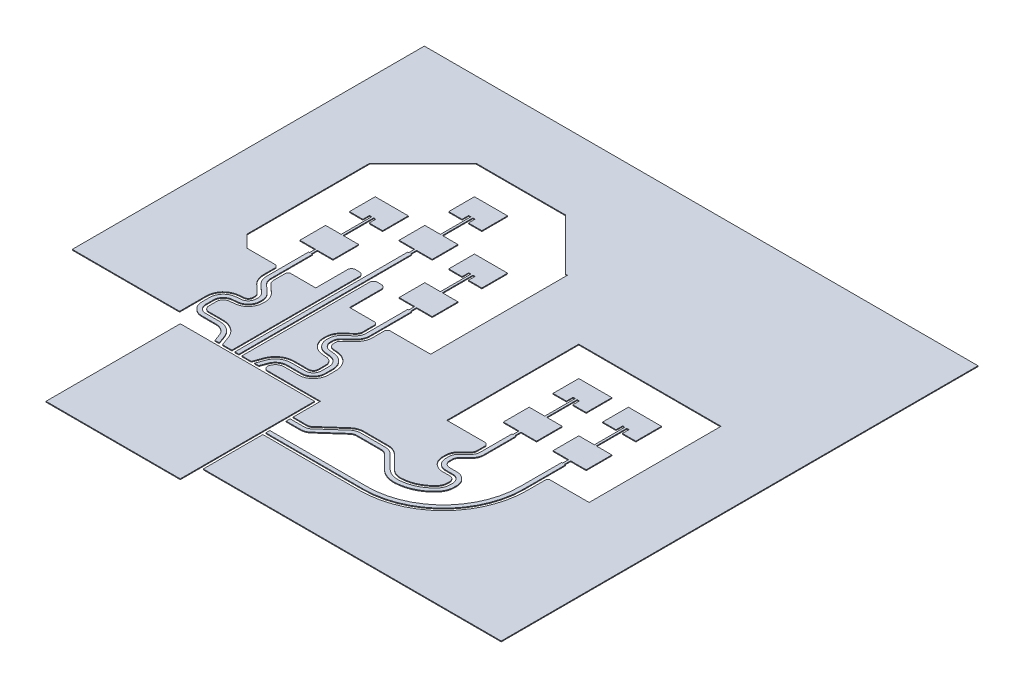
SolidWorks part; units mm, degrees
ref_plane "Front Plane" through (0, 0, 0) normal (0, 0, 1) x (1, 0, 0)
ref_plane "Top Plane" through (0, 0, 0) normal (0, 1, 0) x (1, 0, 0)
ref_plane "Right Plane" through (0, 0, 0) normal (1, 0, 0) x (0, 0, -1)
sketch "Sketch2" plane through (0, 0, 0) normal (0, 1, 0) x (1, 0, 0)
  line L1 (0, 0) -> (0.783, 0)
  line L2 (0, 0) -> (0, 1.294)
  line L3 (0, 1.294) -> (0.783, 1.294)
  line L4 (1.666, 0) -> (1.666, 1.294)
  line L6 (0.783, 1.294) -> (0.783, 2.8313)
  line L8 (0.883, 1.294) -> (0.883, 2.8313)
  line L9 (0.672, 2.8313) -> (0.783, 2.8313)
  line L11 (0, 3.792) -> (1.666, 3.792)
  line L13 (0, 2.498) -> (0.672, 2.498)
  line L14 (0.672, 2.498) -> (0.672, 2.8313)
  line L15 (0.883, 1.294) -> (1.666, 1.294)
  line L16 (0.883, 2.8313) -> (0.994, 2.8313)
  line L17 (0, 1.294) -> (1.666, 0) construction
  line L18 (0, 0) -> (1.666, 1.294) construction
  line L19 (0.833, -1.1816) -> (0.833, 2.0481) construction
  line L20 (0.994, 2.498) -> (0.994, 2.8313)
  line L21 (1.666, 2.498) -> (0.994, 2.498)
  line L23 (0, 3.792) -> (0, 2.498)
  line L24 (0.783, 1.294) -> (0.833, 1.294) construction
  line L25 (0.833, 1.294) -> (0.883, 1.294) construction
  line L26 (1.666, 3.792) -> (1.666, 2.498)
  line L27 (0, 3.792) -> (1.666, 2.498) construction
  line L28 (2.498, 6.29) -> (2.498, 4.996)
  line L29 (4.164, 4.996) -> (3.492, 4.996)
  line L30 (4.164, 2.498) -> (4.164, 3.792)
  line L31 (3.381, 5.3293) -> (3.492, 5.3293)
  line L32 (2.498, 2.498) -> (2.498, 3.792)
  line L33 (3.281, 3.792) -> (3.281, 5.3293)
  line L34 (2.498, 6.29) -> (4.164, 6.29)
  line L35 (2.498, 2.498) -> (4.164, 3.792) construction
  line L36 (3.17, 4.996) -> (3.17, 5.3293)
  line L37 (2.498, 4.996) -> (3.17, 4.996)
  line L38 (3.381, 3.792) -> (3.381, 5.3293)
  line L39 (3.381, 3.792) -> (4.164, 3.792)
  line L40 (2.498, 2.498) -> (3.281, 2.498)
  line L41 (2.498, 3.792) -> (3.281, 3.792)
  line L42 (4.164, 6.29) -> (4.164, 4.996)
  line L43 (3.17, 5.3293) -> (3.281, 5.3293)
  line L44 (3.492, 4.996) -> (3.492, 5.3293)
  line L45 (3.331, 6.29) -> (3.331, 2.498) construction
  line L46 (5.668, 2.8313) -> (5.779, 2.8313)
  line L47 (4.996, 0) -> (4.996, 1.294)
  line L48 (5.99, 2.498) -> (5.99, 2.8313)
  line L49 (5.668, 2.498) -> (5.668, 2.8313)
  line L50 (5.879, 1.294) -> (5.879, 2.8313)
  line L51 (4.996, 1.294) -> (5.779, 1.294)
  line L52 (5.879, 2.8313) -> (5.99, 2.8313)
  line L53 (6.662, 0) -> (6.662, 1.294)
  line L54 (6.662, 3.792) -> (6.662, 2.498)
  line L55 (5.879, 1.294) -> (6.662, 1.294)
  line L56 (4.996, 3.792) -> (4.996, 2.498)
  line L57 (6.662, 2.498) -> (5.99, 2.498)
  line L58 (4.996, 0) -> (5.779, 0)
  line L59 (5.779, 1.294) -> (5.779, 2.8313)
  line L60 (4.996, 2.498) -> (5.668, 2.498)
  line L61 (4.996, 3.792) -> (6.662, 3.792)
  line L62 (5.829, 3.792) -> (5.829, 0) construction
  line L63 (1.666, 2.498) -> (2.498, 2.498) construction
  line L64 (4.164, 2.498) -> (4.996, 2.498) construction
  line L65 (13.721, 0.0293) -> (13.832, 0.0293)
  line L66 (13.721, -0.304) -> (13.721, 0.0293)
  line L67 (13.832, -1.508) -> (13.832, 0.0293)
  line L68 (13.049, -1.508) -> (13.832, -1.508)
  line L69 (14.715, -2.802) -> (14.715, -1.508)
  line L70 (13.932, -1.508) -> (14.715, -1.508)
  line L71 (13.049, -0.304) -> (13.721, -0.304)
  line L72 (13.049, -2.802) -> (13.832, -2.802)
  line L73 (13.049, -2.802) -> (13.049, -1.508)
  line L74 (13.049, 0.99) -> (14.715, 0.99)
  line L75 (14.043, -0.304) -> (14.043, 0.0293)
  line L76 (14.715, -0.304) -> (14.043, -0.304)
  line L77 (13.932, -1.508) -> (13.932, 0.0293)
  line L78 (14.715, 0.99) -> (14.715, -0.304)
  line L79 (13.932, 0.0293) -> (14.043, 0.0293)
  line L80 (13.049, 0.99) -> (13.049, -0.304)
  line L81 (13.882, 0.99) -> (13.882, -2.802) construction
  line L82 (16.33, -1.508) -> (16.33, 0.0293)
  line L83 (15.547, -2.802) -> (15.547, -1.508)
  line L84 (15.547, -1.508) -> (16.33, -1.508)
  line L85 (15.547, -2.802) -> (16.33, -2.802)
  line L86 (16.541, -0.304) -> (16.541, 0.0293)
  line L87 (17.213, 0.99) -> (17.213, -0.304)
  line L88 (15.547, 0.99) -> (17.213, 0.99)
  line L89 (16.38, 0.99) -> (16.38, -2.802) construction
  line L90 (17.213, -2.802) -> (17.213, -1.508)
  line L91 (15.547, 0.99) -> (15.547, -0.304)
  line L92 (17.213, -0.304) -> (16.541, -0.304)
  line L93 (16.219, -0.304) -> (16.219, 0.0293)
  line L94 (15.547, -0.304) -> (16.219, -0.304)
  line L95 (16.43, -1.508) -> (17.213, -1.508)
  line L96 (16.43, -1.508) -> (16.43, 0.0293)
  line L97 (16.43, 0.0293) -> (16.541, 0.0293)
  line L98 (16.219, 0.0293) -> (16.33, 0.0293)
  line L99 (14.715, -0.304) -> (15.547, -0.304) construction
  line L100 (13.049, 0.99) -> (17.213, -2.802) construction
  line L101 (13.049, -2.802) -> (17.213, 0.99) construction
  line L102 (14.715, -2.802) -> (15.547, -2.802) construction
  line L103 (15.131, -2.802) -> (15.131, -0.906) construction
  line L104 (0.783, 0) -> (0.783, -0.3)
  line L105 (0.783, -0.3) -> (0.733, -0.3)
  line L106 (0.733, -0.3) -> (0.733, -1.681)
  line L107 (1.3338, -3.2667) -> (1.402, -3.1936) construction
  line L108 (0.933, -1.1816) -> (0.933, -0.3)
  line L109 (0.933, -0.3) -> (0.883, -0.3)
  line L110 (0.883, -0.3) -> (0.883, 0)
  line L111 (3.281, 2.498) -> (3.281, 2.198)
  line L112 (3.281, 2.198) -> (3.231, 2.198)
  line L113 (3.231, 2.198) -> (3.231, -6.502)
  line L114 (3.231, -6.502) -> (3.431, -6.502)
  line L115 (3.431, -6.502) -> (3.431, 2.198)
  line L116 (3.431, 2.198) -> (3.381, 2.198)
  line L117 (3.381, 2.198) -> (3.381, 2.498)
  line L118 (1.018, -2.8355) -> (1.402, -3.1936) construction
  line L119 (0.321, -4.7757) -> (0.321, -5.162) construction
  line L120 (0.821, -5.662) -> (1.5401, -5.662) construction
  line L121 (2.1979, -6.1226) -> (2.336, -6.502) construction
  line L122 (1.1046, -4.1574) -> (0.8687, -4.178) construction
  line L123 (0.933, -1.1816) -> (0.933, -2.41)
  line L124 (0.833, -2.41) -> (0.833, -1.1816) construction
  line L125 (1.0862, -2.7624) -> (1.4702, -3.1205)
  line L127 (0.421, -4.7757) -> (0.421, -5.162)
  line L128 (0.821, -5.562) -> (1.5401, -5.562)
  line L129 (2.2919, -6.0884) -> (2.4424, -6.502)
  line L130 (0.733, -1.681) -> (0.733, -2.41)
  line L131 (0.9498, -2.9087) -> (1.3338, -3.2667)
  line L133 (0.221, -4.7757) -> (0.221, -5.162)
  line L134 (1.5401, -5.762) -> (0.821, -5.762)
  line L135 (2.1039, -6.1568) -> (2.2296, -6.502)
  line L136 (2.4424, -6.502) -> (2.2296, -6.502)
  line L137 (0.883, 0) -> (1.666, 0)
  line L138 (3.381, 2.498) -> (4.164, 2.498)
  line L139 (3.281, 2.498) -> (3.381, 2.498) construction
  line L140 (16.33, -2.802) -> (16.33, -3.102)
  line L141 (3.331, 2.498) -> (3.331, -6.502) construction
  line L142 (1.402, -3.1936) -> (1.4702, -3.1205) construction
  line L143 (1.561, -3.5593) -> (1.561, -3.6593) construction
  line L144 (5.879, 0) -> (5.879, -0.3)
  line L145 (1.661, -3.5593) -> (1.661, -3.6593)
  line L147 (0.8774, -4.2776) -> (1.1133, -4.257)
  line L148 (1.461, -3.5593) -> (1.461, -3.6593)
  line L150 (5.779, -0.3) -> (5.779, 0)
  line L151 (5.101, -3.5593) -> (5.101, -3.6593) construction
  line L152 (0.86, -4.0784) -> (1.0959, -4.0577)
  line L153 (5.26, -3.1936) -> (5.1918, -3.1205) construction
  line L154 (5.829, -2.41) -> (5.829, -1.1816) construction
  line L155 (5.5574, -4.1574) -> (5.7933, -4.178) construction
  line L156 (4.4641, -6.1226) -> (4.326, -6.502) construction
  line L157 (5.841, -5.662) -> (5.1219, -5.662) construction
  line L158 (6.341, -4.7757) -> (6.341, -5.162) construction
  line L159 (5.644, -2.8355) -> (5.26, -3.1936) construction
  line L160 (5.3282, -3.2667) -> (5.26, -3.1936) construction
  line L161 (5.802, -4.0784) -> (5.5661, -4.0577)
  line L162 (5.201, -3.5593) -> (5.201, -3.6593)
  line L163 (5.7846, -4.2776) -> (5.5487, -4.257)
  line L164 (5.001, -3.5593) -> (5.001, -3.6593)
  line L165 (4.2196, -6.502) -> (4.4324, -6.502)
  line L166 (4.5581, -6.1568) -> (4.4324, -6.502)
  line L167 (5.1219, -5.762) -> (5.841, -5.762)
  line L168 (6.441, -4.7757) -> (6.441, -5.162)
  line L169 (5.7122, -2.9087) -> (5.3282, -3.2667)
  line L170 (5.929, -1.681) -> (5.929, -2.41)
  line L171 (4.3701, -6.0884) -> (4.2196, -6.502)
  line L172 (5.841, -5.562) -> (5.1219, -5.562)
  line L173 (6.241, -4.7757) -> (6.241, -5.162)
  line L174 (5.5758, -2.7624) -> (5.1918, -3.1205)
  line L175 (5.729, -1.1816) -> (5.729, -2.41)
  line L176 (5.729, -0.3) -> (5.779, -0.3)
  line L177 (5.729, -1.1816) -> (5.729, -0.3)
  line L178 (5.929, -0.3) -> (5.929, -1.681)
  line L179 (5.879, -0.3) -> (5.929, -0.3)
  line L180 (5.879, 0) -> (6.662, 0)
  line L181 (16.33, -3.102) -> (16.28, -3.102)
  line L182 (16.28, -3.102) -> (16.28, -5.213)
  line L183 (13.832, -2.802) -> (13.832, -3.102)
  line L184 (16.48, -5.213) -> (16.48, -3.102)
  line L185 (16.48, -3.102) -> (16.43, -3.102)
  line L186 (16.43, -3.102) -> (16.43, -2.802)
  line L187 (12.441, -9.052) -> (7.541, -9.052)
  line L188 (7.541, -9.052) -> (7.541, -9.252)
  line L189 (7.541, -9.252) -> (12.441, -9.252)
  line L191 (16.43, -2.802) -> (17.213, -2.802)
  line L192 (0.631, -6.652) -> (7.391, -6.652)
  line L193 (0.631, -6.652) -> (0.631, -13.412)
  line L194 (0.631, -13.412) -> (7.391, -13.412)
  line L195 (7.391, -6.652) -> (7.391, -13.412)
  line L196 (7.541, -9.152) -> (10.4741, -9.152) construction
  line L197 (13.832, -3.102) -> (13.782, -3.102)
  line L198 (13.782, -3.102) -> (13.782, -4.7207)
  line L199 (13.932, -2.802) -> (14.715, -2.802)
  line L200 (13.982, -4.7207) -> (13.982, -3.102)
  line L201 (13.982, -3.102) -> (13.932, -3.102)
  line L202 (13.932, -3.102) -> (13.932, -2.802)
  line L203 (13.882, -2.802) -> (13.882, -4.7207) construction
  line L204 (13.7356, -5.0742) -> (13.3992, -5.4106) construction
  line L205 (13.282, -5.6935) -> (13.282, -5.8475) construction
  line L206 (13.682, -6.2475) -> (14.0456, -6.2475) construction
  line L207 (14.5456, -6.7475) -> (14.5456, -6.8675) construction
  line L208 (12.1798, -7.7781) -> (11.5201, -7.1184) construction
  line L209 (11.1666, -6.972) -> (9.9359, -6.972) construction
  line L210 (9.6032, -7.0987) -> (8.5857, -8.0053) construction
  line L211 (8.253, -8.132) -> (7.541, -8.132) construction
  line L212 (7.541, -8.132) -> (7.541, -8.032)
  line L213 (7.541, -8.032) -> (8.253, -8.032)
  line L214 (8.5191, -7.9307) -> (9.5367, -7.024)
  line L215 (9.9359, -6.872) -> (11.1666, -6.872)
  line L216 (11.5908, -7.0477) -> (12.2505, -7.7074)
  line L217 (13.6648, -5.0035) -> (13.3284, -5.3399)
  line L218 (13.182, -5.6935) -> (13.182, -5.8475)
  line L219 (13.682, -6.3475) -> (14.0456, -6.3475)
  line L220 (14.4456, -6.7475) -> (14.4456, -6.8675)
  line L221 (13.8063, -5.1449) -> (13.4699, -5.4813)
  line L222 (13.382, -5.6935) -> (13.382, -5.8475)
  line L223 (13.682, -6.1475) -> (14.0456, -6.1475)
  line L224 (14.6456, -6.7475) -> (14.6456, -6.8675)
  line L225 (7.541, -8.132) -> (7.541, -8.232)
  line L226 (7.541, -8.232) -> (8.253, -8.232)
  line L227 (8.6522, -8.08) -> (9.6698, -7.1733)
  line L228 (9.9359, -7.072) -> (11.1666, -7.072)
  line L229 (11.4494, -7.1892) -> (12.1091, -7.8488)
  line L230 (8.262, -1.681) -> (8.262, 5.209)
  line L232 (5.581, 7.79) -> (1.081, 7.79)
  line L233 (1.081, 7.79) -> (-1.6, 5.109)
  line L234 (-1.6, 5.109) -> (-1.6, -1.071)
  line L235 (-1.6, -1.071) -> (-0.99, -1.681)
  line L236 (-0.99, -1.681) -> (0.481, -1.681)
  line L237 (0.581, -1.781) -> (0.581, -2.41)
  line L239 (0.069, -4.7757) -> (0.069, -6.1257)
  line L240 (0.069, -6.1257) -> (-5.331, -6.1257)
  line L241 (-5.331, -6.1257) -> (-5.331, 11.596)
  line L242 (-5.331, 11.596) -> (22.541, 11.596)
  line L243 (22.541, 11.596) -> (22.541, -12.404)
  line L244 (22.541, -12.404) -> (7.541, -12.404)
  line L245 (7.541, -12.404) -> (7.541, -9.404)
  line L246 (7.541, -9.404) -> (12.441, -9.404)
  line L247 (16.632, -5.213) -> (16.632, -4.252)
  line L248 (16.732, -4.152) -> (18.713, -4.152)
  line L249 (18.713, -4.152) -> (18.713, 2.49)
  line L250 (18.713, 2.49) -> (11.549, 2.49)
  line L251 (11.549, 2.49) -> (11.549, -4.152)
  line L252 (11.549, -4.152) -> (13.53, -4.152)
  line L253 (13.63, -4.252) -> (13.63, -4.7207)
  line L260 (6.181, -1.681) -> (8.262, -1.681)
  line L261 (8.262, 5.209) -> (8.162, 5.209)
  line L262 (8.162, 5.209) -> (5.581, 7.79)
  line L263 (3.331, 6.29) -> (3.331, 7.79) construction
  line L264 (0.481, -1.681) -> (0.581, -1.781)
  line L265 (0.8462, -3.0198) -> (1.2301, -3.3779)
  line L266 (1.309, -3.5593) -> (1.309, -3.6593)
  line L267 (1.0826, -3.9063) -> (0.8467, -3.927)
  line L268 (1.085, -1.781) -> (1.085, -2.41)
  line L269 (1.1899, -2.6512) -> (1.5739, -3.0093)
  line L270 (1.813, -3.5593) -> (1.813, -3.6593)
  line L271 (1.1265, -4.4084) -> (0.8907, -4.429)
  line L272 (0.573, -4.7757) -> (0.573, -5.162)
  line L273 (0.821, -5.41) -> (1.5401, -5.41)
  line L274 (2.4347, -6.0364) -> (2.6042, -6.502)
  line L275 (2.6042, -6.502) -> (3.079, -6.502)
  line L276 (3.079, -6.502) -> (3.079, -0.081)
  line L277 (2.879, 0.119) -> (2.679, 0.119)
  line L278 (2.479, -0.081) -> (2.479, -1.681)
  line L279 (2.479, -1.681) -> (1.185, -1.681)
  line L280 (1.185, -1.681) -> (1.085, -1.781)
  line L281 (1.085, -1.781) -> (0.933, -1.781) construction
  line L282 (0.581, -1.781) -> (0.733, -1.781) construction
  line L283 (3.079, 0.119) -> (3.231, 0.119) construction
  line L284 (4.183, -1.681) -> (5.477, -1.681)
  line L285 (4.183, -0.081) -> (4.183, -1.681)
  line L286 (3.783, 0.119) -> (3.983, 0.119)
  line L287 (3.583, -6.502) -> (3.583, -0.081)
  line L288 (4.0578, -6.502) -> (3.583, -6.502)
  line L289 (4.2273, -6.0364) -> (4.0578, -6.502)
  line L290 (5.841, -5.41) -> (5.1219, -5.41)
  line L291 (6.089, -4.7757) -> (6.089, -5.162)
  line L292 (5.5355, -4.4084) -> (5.7713, -4.429)
  line L293 (4.849, -3.5593) -> (4.849, -3.6593)
  line L294 (5.4721, -2.6512) -> (5.0881, -3.0093)
  line L295 (5.577, -1.781) -> (5.577, -2.41)
  line L296 (5.477, -1.681) -> (5.577, -1.781)
  line L297 (6.593, -4.7757) -> (6.593, -5.162)
  line L298 (5.5794, -3.9063) -> (5.8153, -3.927)
  line L299 (5.353, -3.5593) -> (5.353, -3.6593)
  line L300 (5.8158, -3.0198) -> (5.4319, -3.3779)
  line L301 (6.181, -1.681) -> (6.081, -1.781)
  line L302 (6.081, -1.781) -> (6.081, -2.41)
  line L303 (5.841, -5.914) -> (5.1219, -5.914)
  line L304 (4.7009, -6.2088) -> (4.6919, -6.2336)
  line L305 (4.8798, -6.502) -> (7.541, -6.502)
  line L306 (7.541, -6.502) -> (7.541, -7.88)
  line L307 (7.541, -7.88) -> (8.253, -7.88)
  line L308 (8.418, -7.8172) -> (9.4356, -6.9105)
  line L309 (9.9359, -6.72) -> (11.1666, -6.72)
  line L310 (11.6983, -6.9403) -> (12.358, -7.5999)
  line L311 (7.541, -7.88) -> (7.541, -8.032) construction
  line L312 (14.2936, -6.8675) -> (14.2936, -6.7475)
  line L313 (14.0456, -6.4995) -> (13.682, -6.4995)
  line L314 (13.03, -5.8475) -> (13.03, -5.6935)
  line L315 (13.221, -5.2324) -> (13.5574, -4.896)
  line L316 (7.541, -9.252) -> (7.541, -9.404) construction
  line L317 (13.53, -4.152) -> (13.63, -4.252)
  line L318 (16.632, -4.252) -> (16.732, -4.152)
  arc A1 (0.321, -4.7757) -> (0.8687, -4.178) centre (0.921, -4.7757) cw construction
  arc A2 (0.821, -5.662) -> (0.321, -5.162) centre (0.821, -5.162) cw construction
  arc A3 (2.1979, -6.1226) -> (1.5401, -5.662) centre (1.5401, -6.362) ccw construction
  arc A4 (1.561, -3.5593) -> (1.402, -3.1936) centre (1.061, -3.5593) ccw construction
  arc A5 (0.833, -2.41) -> (1.018, -2.8355) centre (1.4148, -2.41) ccw construction
  arc A6 (0.933, -2.41) -> (1.0862, -2.7624) centre (1.4148, -2.41) ccw
  arc A7 (0.421, -4.7757) -> (0.8774, -4.2776) centre (0.921, -4.7757) cw
  arc A8 (0.821, -5.562) -> (0.421, -5.162) centre (0.821, -5.162) cw
  arc A9 (1.5401, -5.562) -> (2.2919, -6.0884) centre (1.5401, -6.362) cw
  arc A10 (0.733, -2.41) -> (0.9498, -2.9087) centre (1.4148, -2.41) ccw
  arc A12 (0.221, -4.7757) -> (0.86, -4.0784) centre (0.921, -4.7757) cw
  arc A13 (0.821, -5.762) -> (0.221, -5.162) centre (0.821, -5.162) cw
  arc A14 (1.5401, -5.762) -> (2.1039, -6.1568) centre (1.5401, -6.362) cw
  arc A15 (1.561, -3.6593) -> (1.1046, -4.1574) centre (1.061, -3.6593) cw construction
  arc A16 (5.101, -3.6593) -> (5.5574, -4.1574) centre (5.601, -3.6593) ccw construction
  arc A17 (1.1133, -4.257) -> (1.661, -3.6593) centre (1.061, -3.6593) ccw
  arc A18 (1.4702, -3.1205) -> (1.661, -3.5593) centre (1.061, -3.5593) cw
  arc A20 (1.3338, -3.2667) -> (1.461, -3.5593) centre (1.061, -3.5593) cw
  arc A22 (1.0959, -4.0577) -> (1.461, -3.6593) centre (1.061, -3.6593) ccw
  arc A23 (5.829, -2.41) -> (5.644, -2.8355) centre (5.2472, -2.41) cw construction
  arc A24 (5.101, -3.5593) -> (5.26, -3.1936) centre (5.601, -3.5593) cw construction
  arc A25 (4.4641, -6.1226) -> (5.1219, -5.662) centre (5.1219, -6.362) cw construction
  arc A26 (5.841, -5.662) -> (6.341, -5.162) centre (5.841, -5.162) ccw construction
  arc A27 (6.341, -4.7757) -> (5.7933, -4.178) centre (5.741, -4.7757) ccw construction
  arc A28 (5.5661, -4.0577) -> (5.201, -3.6593) centre (5.601, -3.6593) cw
  arc A29 (5.3282, -3.2667) -> (5.201, -3.5593) centre (5.601, -3.5593) ccw
  arc A30 (5.1918, -3.1205) -> (5.001, -3.5593) centre (5.601, -3.5593) ccw
  arc A31 (5.5487, -4.257) -> (5.001, -3.6593) centre (5.601, -3.6593) cw
  arc A32 (5.1219, -5.762) -> (4.5581, -6.1568) centre (5.1219, -6.362) ccw
  arc A33 (5.841, -5.762) -> (6.441, -5.162) centre (5.841, -5.162) ccw
  arc A34 (6.441, -4.7757) -> (5.802, -4.0784) centre (5.741, -4.7757) ccw
  arc A35 (5.929, -2.41) -> (5.7122, -2.9087) centre (5.2472, -2.41) cw
  arc A36 (5.1219, -5.562) -> (4.3701, -6.0884) centre (5.1219, -6.362) ccw
  arc A37 (5.841, -5.562) -> (6.241, -5.162) centre (5.841, -5.162) ccw
  arc A38 (6.241, -4.7757) -> (5.7846, -4.2776) centre (5.741, -4.7757) ccw
  arc A39 (5.729, -2.41) -> (5.5758, -2.7624) centre (5.2472, -2.41) cw
  arc A40 (12.441, -9.052) -> (16.28, -5.213) centre (12.441, -5.213) ccw
  arc A41 (16.48, -5.213) -> (12.441, -9.252) centre (12.441, -5.213) cw
  arc A42 (12.9264, -8.0702) -> (14.3444, -7.398) centre (12.8474, -6.0718) ccw construction
  arc A43 (12.9225, -7.9703) -> (14.2696, -7.3317) centre (12.8474, -6.0718) ccw
  arc A44 (12.9304, -8.1702) -> (14.4193, -7.4643) centre (12.8474, -6.0718) ccw
  arc A45 (13.7356, -5.0742) -> (13.882, -4.7207) centre (13.382, -4.7207) ccw construction
  arc A46 (13.6648, -5.0035) -> (13.782, -4.7207) centre (13.382, -4.7207) ccw
  arc A47 (13.982, -4.7207) -> (13.8063, -5.1449) centre (13.382, -4.7207) cw
  arc A48 (13.282, -5.6935) -> (13.3992, -5.4106) centre (13.682, -5.6935) cw construction
  arc A49 (13.182, -5.6935) -> (13.3284, -5.3399) centre (13.682, -5.6935) cw
  arc A50 (13.4699, -5.4813) -> (13.382, -5.6935) centre (13.682, -5.6935) ccw
  arc A51 (13.682, -6.2475) -> (13.282, -5.8475) centre (13.682, -5.8475) cw construction
  arc A52 (13.682, -6.1475) -> (13.382, -5.8475) centre (13.682, -5.8475) cw
  arc A53 (13.682, -6.3475) -> (13.182, -5.8475) centre (13.682, -5.8475) cw
  arc A54 (14.5456, -6.7475) -> (14.0456, -6.2475) centre (14.0456, -6.7475) ccw construction
  arc A55 (14.4456, -6.7475) -> (14.0456, -6.3475) centre (14.0456, -6.7475) ccw
  arc A56 (14.0456, -6.1475) -> (14.6456, -6.7475) centre (14.0456, -6.7475) cw
  arc A57 (14.3444, -7.398) -> (14.5456, -6.8675) centre (13.7456, -6.8675) ccw construction
  arc A58 (14.4193, -7.4643) -> (14.6456, -6.8675) centre (13.7456, -6.8675) ccw
  arc A59 (14.2696, -7.3317) -> (14.4456, -6.8675) centre (13.7456, -6.8675) ccw
  arc A60 (12.1091, -7.8488) -> (12.9304, -8.1702) centre (12.8869, -7.071) ccw
  arc A61 (12.2505, -7.7074) -> (12.9225, -7.9703) centre (12.8869, -7.071) ccw
  arc A62 (12.9264, -8.0702) -> (12.1798, -7.7781) centre (12.8869, -7.071) cw construction
  arc A63 (11.1666, -6.972) -> (11.5201, -7.1184) centre (11.1666, -7.472) cw construction
  arc A64 (11.4494, -7.1892) -> (11.1666, -7.072) centre (11.1666, -7.472) ccw
  arc A65 (11.1666, -6.872) -> (11.5908, -7.0477) centre (11.1666, -7.472) cw
  arc A66 (9.6032, -7.0987) -> (9.9359, -6.972) centre (9.9359, -7.472) cw construction
  arc A67 (9.6698, -7.1733) -> (9.9359, -7.072) centre (9.9359, -7.472) cw
  arc A68 (9.5367, -7.024) -> (9.9359, -6.872) centre (9.9359, -7.472) cw
  arc A69 (8.253, -8.132) -> (8.5857, -8.0053) centre (8.253, -7.632) ccw construction
  arc A70 (8.253, -8.232) -> (8.6522, -8.08) centre (8.253, -7.632) ccw
  arc A71 (8.5191, -7.9307) -> (8.253, -8.032) centre (8.253, -7.632) cw
  arc A72 (0.069, -4.7757) -> (0.8467, -3.927) centre (0.921, -4.7757) cw
  arc A73 (0.8462, -3.0198) -> (0.581, -2.41) centre (1.4148, -2.41) cw
  arc A74 (1.309, -3.5593) -> (1.2301, -3.3779) centre (1.061, -3.5593) ccw
  arc A75 (1.309, -3.6593) -> (1.0826, -3.9063) centre (1.061, -3.6593) cw
  arc A76 (1.1899, -2.6512) -> (1.085, -2.41) centre (1.4148, -2.41) cw
  arc A77 (1.813, -3.5593) -> (1.5739, -3.0093) centre (1.061, -3.5593) ccw
  arc A78 (1.813, -3.6593) -> (1.1265, -4.4084) centre (1.061, -3.6593) cw
  arc A79 (0.8907, -4.429) -> (0.573, -4.7757) centre (0.921, -4.7757) ccw
  arc A80 (0.821, -5.41) -> (0.573, -5.162) centre (0.821, -5.162) cw
  arc A81 (2.4347, -6.0364) -> (1.5401, -5.41) centre (1.5401, -6.362) ccw
  arc A82 (2.479, -0.081) -> (2.679, 0.119) centre (2.679, -0.081) cw
  arc A83 (3.079, -0.081) -> (2.879, 0.119) centre (2.879, -0.081) ccw
  arc A84 (4.183, -0.081) -> (3.983, 0.119) centre (3.983, -0.081) ccw
  arc A85 (3.583, -0.081) -> (3.783, 0.119) centre (3.783, -0.081) cw
  arc A86 (4.2273, -6.0364) -> (5.1219, -5.41) centre (5.1219, -6.362) cw
  arc A87 (5.841, -5.41) -> (6.089, -5.162) centre (5.841, -5.162) ccw
  arc A88 (5.7713, -4.429) -> (6.089, -4.7757) centre (5.741, -4.7757) cw
  arc A89 (4.849, -3.6593) -> (5.5355, -4.4084) centre (5.601, -3.6593) ccw
  arc A90 (4.849, -3.5593) -> (5.0881, -3.0093) centre (5.601, -3.5593) cw
  arc A91 (5.4721, -2.6512) -> (5.577, -2.41) centre (5.2472, -2.41) ccw
  arc A92 (6.593, -4.7757) -> (5.8153, -3.927) centre (5.741, -4.7757) ccw
  arc A93 (5.353, -3.6593) -> (5.5794, -3.9063) centre (5.601, -3.6593) ccw
  arc A94 (5.353, -3.5593) -> (5.4319, -3.3779) centre (5.601, -3.5593) cw
  arc A95 (5.8158, -3.0198) -> (6.081, -2.41) centre (5.2472, -2.41) ccw
  arc A96 (6.593, -5.162) -> (5.841, -5.914) centre (5.841, -5.162) cw
  arc A97 (4.7009, -6.2088) -> (5.1219, -5.914) centre (5.1219, -6.362) cw
  arc A98 (4.8798, -6.502) -> (4.6919, -6.2336) centre (4.8798, -6.302) cw
  arc A99 (8.418, -7.8172) -> (8.253, -7.88) centre (8.253, -7.632) cw
  arc A100 (9.9359, -6.72) -> (9.4356, -6.9105) centre (9.9359, -7.472) ccw
  arc A101 (11.6983, -6.9403) -> (11.1666, -6.72) centre (11.1666, -7.472) ccw
  arc A102 (12.358, -7.5999) -> (12.9165, -7.8184) centre (12.8869, -7.071) ccw
  arc A103 (12.9165, -7.8184) -> (14.1558, -7.2309) centre (12.8474, -6.0718) ccw
  arc A104 (14.1558, -7.2309) -> (14.2936, -6.8675) centre (13.7456, -6.8675) ccw
  arc A105 (14.2936, -6.7475) -> (14.0456, -6.4995) centre (14.0456, -6.7475) ccw
  arc A106 (13.03, -5.8475) -> (13.682, -6.4995) centre (13.682, -5.8475) ccw
  arc A107 (13.03, -5.6935) -> (13.221, -5.2324) centre (13.682, -5.6935) cw
  arc A108 (13.63, -4.7207) -> (13.5574, -4.896) centre (13.382, -4.7207) cw
  arc A109 (16.632, -5.213) -> (12.441, -9.404) centre (12.441, -5.213) cw
  point P9 (0.833, 3.145)
  point P17 (0.833, 0.647)
  point P165 (0.833, -6.3085)
  point P166 (3.331, -6.502)
  point P181 (2.8666, -5.436)
  point P226 (5.829, -6.3085)
  point P286 (13.882, -4.9278)
  point P342 (8.431, -8.0993)
  point P344 (0.581, -1.681)
  point P345 (9.7579, -7.0047)
  point P346 (11.3579, -7.0101)
  point P349 (12.5225, -8.0023)
  point P353 (13.3124, -5.5404)
  point P354 (13.3992, -6.1304)
  point P358 (13.8439, -4.912)
  point P359 (14.3992, -6.394)
  point P362 (16.632, -4.152)
  point P369 (13.63, -4.152)
  point P447 (1.309, -3.6093)
  point P453 (5.353, -3.6093)
  dimension "D13" = 0.6
  dimension "D14" = 0.5
  dimension "D15" = 0.7
  dimension "D16" = 0.5
  dimension "D17" = 2.11
  dimension "D19" = 1.484
  dimension "D23" = 0.84
  dimension "D25" = 0.995
  dimension "D26" = 0.1
  dimension "D20" = 0.5
  dimension "D27" = 1.77
  dimension "D36" = 4.9
  dimension "D37" = 0.8
  dimension "D41" = 138.3
  dimension "D42" = 0.12
  dimension "D51" = 0.5
  dimension "D52" = 0.4
  dimension "D53" = 2.11
  dimension "D54" = 0.4
  dimension "D55" = 1
  dimension "D56" = 2
  dimension "D57" = 1.6
  dimension "D58" = 45
  dimension "D59" = 1.5
  dimension "D60" = 0.5
  dimension "D61" = 0.1
  dimension "D62" = 1.6
  dimension "D63" = 4.5
  dimension "D64" = 6.18
  dimension "D65" = 0.152
  dimension "D66" = 6.89
  dimension "D67" = 1.5
  dimension "D68" = 0.5
  dimension "D70" = 0.5
  dimension "D71" = 1.5
  dimension "D38" = 1.02
  dimension "D39" = 1.53
  dimension "D40" = 135
  dimension "D44" = 1.16
  dimension "D50" = 0.5
  dimension "D77" = 0.2
  dimension "D78" = 1.8
  dimension "D79" = 0.6
  dimension "D80" = 0.5818
  dimension "D81" = 0.525
  dimension "D82" = 0.2368
  dimension "D83" = 0.3863
  dimension "D109" = 3.839
  dimension "D75" = 5.4
  dimension "D114" = 1.35
  dimension "D115" = 0.2
  dimension "D118" = 0.852
  dimension "D121" = 0.248
  dimension "D123" = 0.1
  dimension "D124" = 0.248
  dimension "D125" = 0.8338
  dimension "D136" = 0.752
  dimension "D139" = 0.448
  dimension "D145" = 0.248
  dimension "D146" = 0.752
  dimension "D147" = 0.752
  dimension "D148" = 0.748
  dimension "D149" = 1.748
  dimension "D150" = 0.548
  dimension "D151" = 0.652
  dimension "D152" = 0.652
  dimension "D153" = 0.248
  dimension "D160" = 4.191
  dimension "D1" = 1.666
  dimension "D2" = 1.294
  dimension "D3" = 11.8
  dimension "D4" = 0.3333
  dimension "D5" = 0.111
  dimension "D6" = 0.1
  dimension "D7" = 2.498
  dimension "D8" = 2.498
  dimension "D9" = 5.3
  dimension "D10" = 0.2
  dimension "D11" = 0.3
  dimension "D12" = 8.7
  dimension "D18" = 47
  dimension "D21" = 3.01
  dimension "D22" = 0.2
  dimension "D24" = 70
  dimension "D28" = 5
  dimension "D29" = 0.2
  dimension "D30" = 6.76
  dimension "D31" = 0.15
  dimension "D32" = 2.7
  dimension "D33" = 0.15
  dimension "D34" = 6.25
  dimension "D35" = 6.76
  dimension "D43" = 0.89
  dimension "D45" = 1.6
  dimension "D46" = 0.59
  dimension "D47" = 135
  dimension "D48" = 0.6
  dimension "D49" = 1
  dimension "D72" = 1.5
  dimension "D73" = 1.681
  dimension "D74" = 1.35
  dimension "D76" = 0.1
  dimension "D84" = 0.7191
  dimension "D85" = 0.4038
  dimension "D86" = 47
  dimension "D87" = 47
  dimension "D88" = 85
  dimension "D89" = 85
  dimension "D90" = 90
  dimension "D91" = 70
  dimension "D92" = 41.7
  dimension "D93" = 0.712
  dimension "D94" = 1.3629
  dimension "D95" = 41.7
  dimension "D96" = 1.2307
  dimension "D97" = 45
  dimension "D98" = 0.9329
  dimension "D99" = 47.265
  dimension "D100" = 46.198
  dimension "D101" = 41.538
  dimension "D102" = 90
  dimension "D103" = 90
  dimension "D104" = 45
  dimension "D105" = 0.1541
  dimension "D106" = 0.4757
  dimension "D107" = 45
  dimension "D108" = 1.9187
  dimension "D110" = 90
  dimension "D111" = 2.111
  dimension "D112" = 4.9
  dimension "D113" = 0.3636
  dimension "D119" = 85
  dimension "D120" = 0.2368
  dimension "D122" = 85
  dimension "D126" = 0.629
  dimension "D127" = 0.1414
  dimension "D128" = 1.471
  dimension "D129" = 45
  dimension "D130" = 0.8627
  dimension "D131" = 3.7915
  dimension "D132" = 3.6501
  dimension "D133" = 6.89
  dimension "D134" = 2.081
  dimension "D135" = 0.3863
  dimension "D137" = 90
  dimension "D138" = 0.7191
  dimension "D140" = 70
  dimension "D141" = 0.0264
  dimension "D142" = 110
  dimension "D143" = 2.6612
  dimension "D144" = 1.378
  dimension "D154" = 0.4687
  dimension "D155" = 1.981
  dimension "D156" = 6.642
  dimension "D157" = 7.164
  dimension "D158" = 1.981
  dimension "D159" = 0.961
  dimension "D161" = 3
  dimension "D162" = 15
  dimension "D163" = 24
  dimension "D164" = 27.872
  dimension "D165" = 17.7217
extrude "Boss-Extrude1" add sketch "Sketch2" along normal blind 0.0406
ref_axis "Axis1" through (3.331, 0.0406, -6.29) along (-0.1156, 0, 0.9933)
